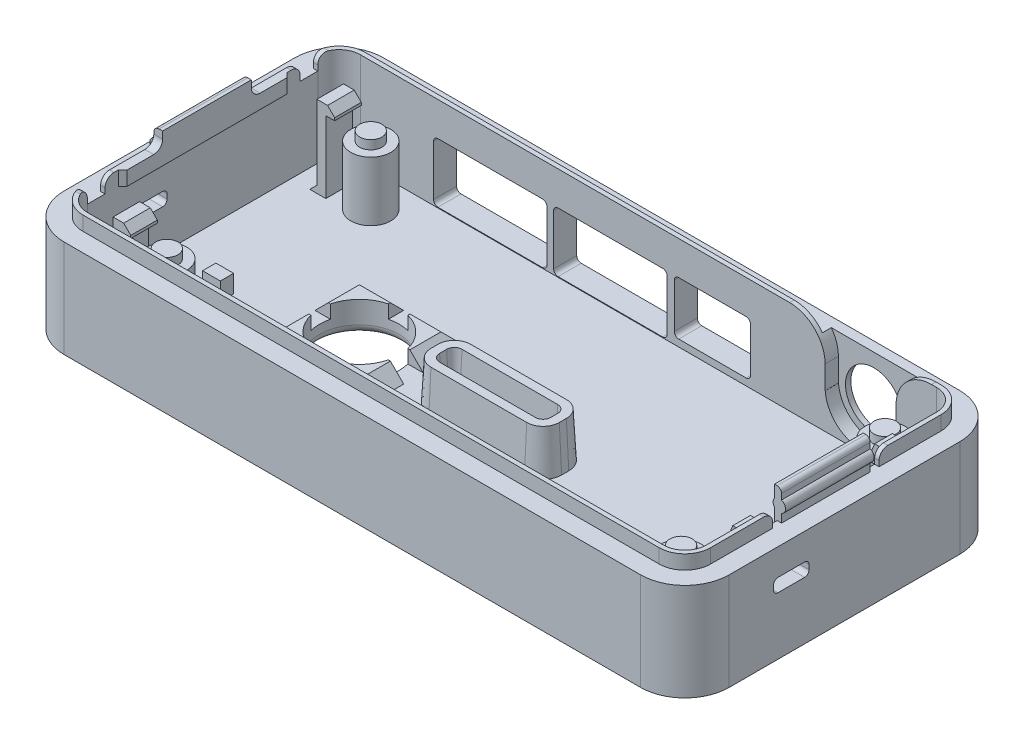
SolidWorks part; units mm, degrees
ref_plane "前视基准面" through (0, 0, 0) normal (0, 0, 1) x (1, 0, 0)
ref_plane "上视基准面" through (0, 0, 0) normal (0, 1, 0) x (1, 0, 0)
ref_plane "右视基准面" through (0, 0, 0) normal (1, 0, 0) x (0, 0, -1)
sketch "zero" plane through (0, 0, 0) normal (0, 1, 0) x (1, 0, 0)
  line L1 (-29.5, 15) -> (29.5, 15)
  line L2 (-32.5, 12) -> (-32.5, -12)
  line L3 (-29.5, -15) -> (29.5, -15)
  line L4 (32.5, 12) -> (32.5, -12)
  line L5 (-32.5, 15) -> (32.5, -15) construction
  line L6 (-32.5, -15) -> (32.5, 15) construction
  line L7 (-25.7, -15) -> (-14.5, -15)
  line L8 (-25.7, -15) -> (-25.7, -9.6569)
  line L9 (-25.7, -9.6569) -> (-14.5, -9.6569)
  line L10 (-14.5, -15) -> (-14.5, -9.6569)
  line L11 (5.2, -15) -> (12.7, -15)
  line L12 (5.2, -15) -> (5.2, -11)
  line L13 (5.2, -11) -> (12.7, -11)
  line L14 (12.7, -15) -> (12.7, -11)
  line L15 (17.8, -15) -> (25.3, -15)
  line L16 (17.8, -15) -> (17.8, -11)
  line L17 (17.8, -11) -> (25.3, -11)
  line L18 (25.3, -15) -> (25.3, -11)
  line L19 (-32.5, 7.7) -> (-19.5, 7.7)
  line L20 (-32.5, 7.7) -> (-32.5, -4.3)
  line L21 (-32.5, -4.3) -> (-19.5, -4.3)
  line L22 (-19.5, 7.7) -> (-19.5, -4.3)
  line L23 (-25.5, 14) -> (25.5, 14)
  line L24 (-25.5, 14) -> (-25.5, 8.8)
  line L25 (-25.5, 8.8) -> (25.5, 8.8)
  line L26 (25.5, 14) -> (25.5, 8.8)
  line L27 (-19.5, 7.2329) -> (-35.5, 7.2329)
  line L28 (-19.5, 7.2329) -> (-19.5, -3.7671)
  line L29 (-19.5, -3.7671) -> (-35.5, -3.7671)
  line L30 (-35.5, 7.2329) -> (-35.5, -3.7671)
  arc A0 (29.5, -15) -> (32.5, -12) centre (29.5, -12) ccw
  arc A1 (29.5, 15) -> (32.5, 12) centre (29.5, 12) cw
  arc A2 (-32.5, -12) -> (-29.5, -15) centre (-29.5, -12) ccw
  arc A3 (-29.5, 15) -> (-32.5, 12) centre (-29.5, 12) ccw
  circle A4 centre (-29, 11.4) radius 3
  circle A5 centre (-29, -11.5) radius 3
  circle A6 centre (29, 11.4) radius 3
  circle A7 centre (29, -11.5) radius 3
  circle A8 centre (-29, 11.4) radius 1.375
  circle A9 centre (-29, -11.5) radius 1.375
  circle A10 centre (29, -11.5) radius 1.375
  circle A11 centre (29, 11.4) radius 1.375
  point P0 (0, 0)
  dimension "D3" = 3
  dimension "D4" = 6
  dimension "D9" = 2.75
  dimension "D1" = 65
  dimension "D2" = 30
  dimension "D5" = 3.6
  dimension "D6" = 3.5
  dimension "D7" = 3.5
  dimension "D8" = 3.5
  dimension "D10" = 12
  dimension "D11" = 7.3
  dimension "D12" = 13
  dimension "D13" = 11.2
  dimension "D14" = 6.8
  dimension "D15" = 19.7
  dimension "D16" = 7.5
  dimension "D17" = 7.5
  dimension "D18" = 5.1
  dimension "D19" = 4
  dimension "D20" = 5.2
  dimension "D21" = 7
  dimension "D22" = 7
  dimension "D23" = 1
  dimension "D24" = 11
  dimension "D25" = 16
sketch "sugar" plane through (0, 0, 0) normal (0, 1, 0) x (1, 0, 0)
  line L1 (-29.5, 15) -> (29.5, 15)
  line L2 (-32.5, 12) -> (-32.5, -12)
  line L3 (-29.5, -15) -> (29.5, -15)
  line L4 (32.5, 12) -> (32.5, -12)
  line L5 (-32.5, 15) -> (32.5, -15) construction
  line L6 (-32.5, -15) -> (32.5, 15) construction
  line L7 (23.5, -11.5) -> (19.5, -11.5)
  line L8 (23.5, -11.5) -> (23.5, -13.9082)
  line L9 (23.5, -13.9082) -> (19.5, -13.9082)
  line L10 (19.5, -11.5) -> (19.5, -13.9082)
  line L11 (16, -11.0071) -> (8.5, -11.0071)
  line L12 (16, -11.0071) -> (16, -15)
  line L13 (16, -15) -> (8.5, -15)
  line L14 (8.5, -11.0071) -> (8.5, -15)
  line L15 (20.5, -13.9082) -> (22.5, -13.9082)
  line L16 (20.5, -13.9082) -> (20.5, -14.8173)
  line L17 (20.5, -14.8173) -> (22.5, -14.8173)
  line L18 (22.5, -13.9082) -> (22.5, -14.8173)
  arc A0 (29.5, 15) -> (32.5, 12) centre (29.5, 12) cw
  arc A1 (29.5, -15) -> (32.5, -12) centre (29.5, -12) ccw
  arc A2 (-32.5, -12) -> (-29.5, -15) centre (-29.5, -12) ccw
  arc A3 (-29.5, 15) -> (-32.5, 12) centre (-29.5, 12) ccw
  circle A4 centre (-29, 11.4) radius 3
  circle A5 centre (-29, 11.4) radius 1.375
  circle A6 centre (-29, -11.5) radius 3
  circle A7 centre (-29, -11.5) radius 1.375
  circle A8 centre (29, 11.4) radius 3
  circle A9 centre (29, 11.4) radius 1.375
  circle A10 centre (29, -11.5) radius 3
  circle A11 centre (29, -11.5) radius 1.375
  dimension "D3" = 3
  dimension "D1" = 65
  dimension "D2" = 30
  dimension "D4" = 9
  dimension "D5" = 4
  dimension "D6" = 3.5
  dimension "D7" = 7.5
  dimension "D8" = 2
  dimension "D9" = 1
sketch "case" plane through (0, 0, 0) normal (0, 1, 0) x (1, 0, 0)
  line L1 (-34.0422, 18) -> (30.9578, 18)
  line L2 (-39.0422, 13) -> (-39.0422, -13)
  line L3 (-34.0422, -18) -> (30.9578, -18)
  line L4 (35.9578, 13) -> (35.9578, -13)
  line L5 (-39.0422, 18) -> (35.9578, -18) construction
  line L6 (-39.0422, -18) -> (35.9578, 18) construction
  arc A0 (-39.0422, -13) -> (-34.0422, -18) centre (-34.0422, -13) ccw
  arc A1 (30.9578, -18) -> (35.9578, -13) centre (30.9578, -13) ccw
  arc A2 (30.9578, 18) -> (35.9578, 13) centre (30.9578, 13) cw
  arc A3 (-34.0422, 18) -> (-39.0422, 13) centre (-34.0422, 13) ccw
  point P0 (-1.5422, 0)
  point P3 (-1.5422, 0)
  dimension "D3" = 5
  dimension "D1" = 75
  dimension "D2" = 36
extrude "凸台-拉伸2" add sketch "case" along normal blind 11
sketch "草图2" plane through (0, 0, 0) normal (0, 1, 0) x (1, 0, 0)
  line L4 (-34.0422, -15.4) -> (30.9578, -15.4)
  line L5 (33.3578, -13) -> (33.3578, 13)
  line L6 (30.9578, 15.4) -> (-34.0422, 15.4)
  line L7 (-36.4422, 13) -> (-36.4422, -13)
  line L8 (33.8578, -13) -> (33.8578, 13)
  line L9 (30.9578, 15.9) -> (-34.0422, 15.9)
  line L10 (-36.9422, 13) -> (-36.9422, -13)
  line L11 (-34.0422, -15.9) -> (30.9578, -15.9)
  line L12 (33.8578, -13) -> (33.8578, 13)
  line L13 (30.9578, 15.9) -> (-34.0422, 15.9)
  line L14 (-36.9422, 13) -> (-36.9422, -13)
  line L15 (-34.0422, -15.9) -> (30.9578, -15.9)
  arc A4 (30.9578, -15.4) -> (33.3578, -13) centre (30.9578, -13) ccw
  arc A5 (33.3578, 13) -> (30.9578, 15.4) centre (30.9578, 13) ccw
  arc A6 (-34.0422, 15.4) -> (-36.4422, 13) centre (-34.0422, 13) ccw
  arc A7 (-36.4422, -13) -> (-34.0422, -15.4) centre (-34.0422, -13) ccw
  arc A8 (30.9578, -15.9) -> (33.8578, -13) centre (30.9578, -13) ccw
  arc A9 (33.8578, 13) -> (30.9578, 15.9) centre (30.9578, 13) ccw
  arc A10 (-34.0422, 15.9) -> (-36.9422, 13) centre (-34.0422, 13) ccw
  arc A11 (-36.9422, -13) -> (-34.0422, -15.9) centre (-34.0422, -13) ccw
  arc A12 (30.9578, -15.9) -> (33.8578, -13) centre (30.9578, -13) ccw
  arc A13 (33.8578, 13) -> (30.9578, 15.9) centre (30.9578, 13) ccw
  arc A14 (-34.0422, 15.9) -> (-36.9422, 13) centre (-34.0422, 13) ccw
  arc A15 (-36.9422, -13) -> (-34.0422, -15.9) centre (-34.0422, -13) ccw
  dimension "D1" = 2.1
  dimension "D2" = 0.5
ref_plane "基准面1" through (0, 11, 0) normal (0, 1, 0) x (1, 0, 0)
sketch "草图3" plane through (0, 11, 0) normal (0, 1, 0) x (1, 0, 0)
  line L4 (-34.0422, -15.4) -> (30.9578, -15.4)
  line L5 (33.3578, -13) -> (33.3578, 13)
  line L6 (30.9578, 15.4) -> (-34.0422, 15.4)
  line L7 (-36.4422, 13) -> (-36.4422, -13)
  line L8 (-34.0422, -15.4) -> (30.9578, -15.4)
  line L9 (33.3578, -13) -> (33.3578, 13)
  line L10 (30.9578, 15.4) -> (-34.0422, 15.4)
  line L11 (-36.4422, 13) -> (-36.4422, -13)
  line L12 (-36.9422, 13) -> (-36.9422, -13)
  line L13 (-34.0422, -15.9) -> (30.9578, -15.9)
  line L14 (33.8578, -13) -> (33.8578, 13)
  line L15 (30.9578, 15.9) -> (-34.0422, 15.9)
  line L16 (-36.9422, 13) -> (-36.9422, -13)
  line L17 (-34.0422, -15.9) -> (30.9578, -15.9)
  line L18 (33.8578, -13) -> (33.8578, 13)
  line L19 (30.9578, 15.9) -> (-34.0422, 15.9)
  arc A4 (30.9578, -15.4) -> (33.3578, -13) centre (30.9578, -13) ccw
  arc A5 (33.3578, 13) -> (30.9578, 15.4) centre (30.9578, 13) ccw
  arc A6 (-34.0422, 15.4) -> (-36.4422, 13) centre (-34.0422, 13) ccw
  arc A7 (-36.4422, -13) -> (-34.0422, -15.4) centre (-34.0422, -13) ccw
  arc A8 (30.9578, -15.4) -> (33.3578, -13) centre (30.9578, -13) ccw
  arc A9 (33.3578, 13) -> (30.9578, 15.4) centre (30.9578, 13) ccw
  arc A10 (-34.0422, 15.4) -> (-36.4422, 13) centre (-34.0422, 13) ccw
  arc A11 (-36.4422, -13) -> (-34.0422, -15.4) centre (-34.0422, -13) ccw
  arc A12 (-36.9422, -13) -> (-34.0422, -15.9) centre (-34.0422, -13) ccw
  arc A13 (30.9578, -15.9) -> (33.8578, -13) centre (30.9578, -13) ccw
  arc A14 (33.8578, 13) -> (30.9578, 15.9) centre (30.9578, 13) ccw
  arc A15 (-34.0422, 15.9) -> (-36.9422, 13) centre (-34.0422, 13) ccw
  arc A16 (-36.9422, -13) -> (-34.0422, -15.9) centre (-34.0422, -13) ccw
  arc A17 (30.9578, -15.9) -> (33.8578, -13) centre (30.9578, -13) ccw
  arc A18 (33.8578, 13) -> (30.9578, 15.9) centre (30.9578, 13) ccw
  arc A19 (-34.0422, 15.9) -> (-36.9422, 13) centre (-34.0422, 13) ccw
  dimension "D1" = 0
  dimension "D2" = 0
extrude "凸台-拉伸4" add sketch "草图3" along normal blind 1.6
sketch "草图5" plane through (0, 11, 0) normal (0, 1, 0) x (1, 0, 0)
  line L0 (33.3578, -13) -> (33.3578, 13) construction
  line L1 (33.0578, 5) -> (33.3578, 5)
  line L2 (33.0578, 5) -> (33.0578, -5)
  line L3 (33.0578, -5) -> (33.3578, -5)
  line L4 (33.3578, 5) -> (33.3578, -5)
  line L5 (33.0578, 5) -> (33.3578, -5) construction
  line L6 (33.0578, -5) -> (33.3578, 5) construction
  point P0 (33.2078, 0)
  dimension "D2" = 10
  dimension "D3" = 0.3
  dimension "D4" = 0
ref_plane "基准面3" through (33.8578, 0, 0) normal (1, 0, 0) x (0, 0, -1)
ref_plane "基准面7" through (-36.9422, 0, 0) normal (-1, 0, 0) x (0, 0, 1)
ref_plane "基准面8" through (0, 0, 0) normal (0, -1, 0) x (-1, 0, 0)
sketch "草图14" plane through (0, 11, 0) normal (0, 1, 0) x (1, 0, 0)
  line L4 (-34.0422, -15.4) -> (30.9578, -15.4)
  line L5 (33.3578, -13) -> (33.3578, 13)
  line L6 (30.9578, 15.4) -> (-34.0422, 15.4)
  line L7 (-36.4422, 13) -> (-36.4422, -13)
  line L8 (-34.0422, -15.4) -> (30.9578, -15.4)
  line L9 (33.3578, -13) -> (33.3578, 13)
  line L10 (30.9578, 15.4) -> (-34.0422, 15.4)
  line L11 (-36.4422, 13) -> (-36.4422, -13)
  arc A4 (30.9578, -15.4) -> (33.3578, -13) centre (30.9578, -13) ccw
  arc A5 (33.3578, 13) -> (30.9578, 15.4) centre (30.9578, 13) ccw
  arc A6 (-34.0422, 15.4) -> (-36.4422, 13) centre (-34.0422, 13) ccw
  arc A7 (-36.4422, -13) -> (-34.0422, -15.4) centre (-34.0422, -13) ccw
  arc A8 (30.9578, -15.4) -> (33.3578, -13) centre (30.9578, -13) ccw
  arc A9 (33.3578, 13) -> (30.9578, 15.4) centre (30.9578, 13) ccw
  arc A10 (-34.0422, 15.4) -> (-36.4422, 13) centre (-34.0422, 13) ccw
  arc A11 (-36.4422, -13) -> (-34.0422, -15.4) centre (-34.0422, -13) ccw
  dimension "D1" = 0
extrude "切除-拉伸2" cut sketch "草图14" against normal blind 9
extrude "凸台-拉伸12" add sketch "草图5" against normal blind 2 and the other way blind 1.6
sketch "草图15" plane through (0, 2, 0) normal (0, 1, 0) x (1, 0, 0)
  line L1 (35.9578, -13) -> (35.9578, 13) construction
  line L5 (-39.0422, 13) -> (-39.0422, -13) construction
  line L6 (-34.0422, -18) -> (30.9578, -18) construction
  line L7 (30.9578, 18) -> (-34.0422, 18) construction
  circle A0 centre (29.0603, -11.5295) radius 2.25
  circle A1 centre (-28.9397, -11.5295) radius 2.25
  circle A2 centre (29.0603, 11.4705) radius 2.25
  circle A3 centre (-28.9397, 11.4705) radius 2.25
  dimension "D1" = 4.5
  dimension "D2" = 6.8975
  dimension "D3" = 10.1025
  dimension "D4" = 6.4705
  dimension "D5" = 6.5295
extrude "凸台-拉伸13" add sketch "草图15" along normal blind 6.7
sketch "草图16" plane through (0, 8.7, 0) normal (0, 1, 0) x (1, 0, 0)
  circle A0 centre (29.0603, -11.5295) radius 1.25
  circle A1 centre (29.0603, 11.4705) radius 1.25
  circle A2 centre (-28.9397, -11.5295) radius 1.25
  circle A3 centre (-28.9397, 11.4705) radius 1.25
  point P12 (0, 0)
  dimension "D1" = 2.5
extrude "凸台-拉伸14" add sketch "草图16" along normal blind 1
sketch "草图17" plane through (0, 12.6, 0) normal (0, 1, 0) x (1, 0, 0)
  line L0 (33.3578, -13) -> (33.3578, -5) construction
  line L1 (33.3578, -5) -> (33.8578, -5)
  line L2 (33.3578, -5) -> (33.3578, -6)
  line L3 (33.3578, -6) -> (33.8578, -6)
  line L4 (33.8578, -5) -> (33.8578, -6)
  line L5 (33.3578, -13) -> (33.3578, 13) construction
  line L6 (33.8578, -13) -> (33.8578, 13) construction
  line L8 (33.3578, 5) -> (33.8578, 5)
  line L9 (33.3578, 5) -> (33.3578, 6)
  line L10 (33.3578, 6) -> (33.8578, 6)
  line L11 (33.8578, 5) -> (33.8578, 6)
  dimension "D1" = 1
  dimension "D2" = 1
extrude "切除-拉伸3" cut sketch "草图17" against normal blind 1.6
sketch "草图19" plane through (0, 12.6, 0) normal (0, 1, 0) x (1, 0, 0)
  line L0 (33.0578, 5) -> (33.0578, -5) construction
  line L1 (33.8578, -5) -> (33.0578, -5)
  line L2 (33.8578, -5) -> (33.8578, 5)
  line L3 (33.8578, 5) -> (33.0578, 5)
  line L4 (33.0578, -5) -> (33.0578, 5)
extrude "凸台-拉伸15" add sketch "草图19" along normal blind 1.8
sketch "草图20" plane through (0, 0, -5) normal (0, 0, -1) x (-1, 0, 0)
  line L0 (-30.9578, 11) -> (-35.9578, 11) construction
  line L3 (-33.8578, 11) -> (-33.8578, 14.4) construction
  circle A0 centre (-33.6078, 12.6) radius 0.7
  dimension "D1" = 1.4
  dimension "D2" = 1.6
  dimension "D3" = 0.25
extrude "凸台-拉伸16" add sketch "草图20" against normal blind 10
fillet "圆角4" radius 0.5 1 edges at (33.8578, 14.4, 0)
sketch "草图39" plane through (0, 0, -18) normal (0, 0, -1) x (-1, 0, 0)
  line L0 (-30.9578, 0) -> (34.0422, 0) construction
  line L1 (-35.9578, 11) -> (-35.9578, 0) construction
  circle A0 centre (-22.3721, 6.2789) radius 4
  dimension "D1" = 6.2789
  dimension "D3" = 8
  dimension "D2" = 13.5857
extrude "切除-拉伸4" cut sketch "草图39" against normal blind 0.5
sketch "草图41" plane through (0, 0, -18) normal (0, 0, -1) x (-1, 0, 0)
  line L0 (-30.9578, 0) -> (34.0422, 0) construction
  line L1 (-9.9578, 2.7789) -> (-1.3578, 2.7789)
  line L2 (-9.9578, 2.7789) -> (-9.9578, 8.7789)
  line L3 (-9.9578, 8.7789) -> (-1.3578, 8.7789)
  line L4 (-1.3578, 2.7789) -> (-1.3578, 8.7789)
  line L5 (-0.5578, 2.0789) -> (12.2422, 2.0789)
  line L6 (-0.5578, 2.0789) -> (-0.5578, 8.7789)
  line L7 (-0.5578, 8.7789) -> (12.2422, 8.7789)
  line L8 (12.2422, 2.0789) -> (12.2422, 8.7789)
  line L9 (12.9922, 2.0789) -> (25.7922, 2.0789)
  line L10 (12.9922, 2.0789) -> (12.9922, 8.7789)
  line L11 (12.9922, 8.7789) -> (25.7922, 8.7789)
  line L12 (25.7922, 2.0789) -> (25.7922, 8.7789)
  line L13 (-35.9578, 11) -> (-35.9578, 0) construction
  dimension "D1" = 8.7789
  dimension "D2" = 26
  dimension "D3" = 8.6
  dimension "D4" = 6
  dimension "D5" = 0.8
  dimension "D6" = 6.7
  dimension "D7" = 12.8
  dimension "D8" = 0.75
  dimension "D9" = 12.8
extrude "切除-拉伸5" cut sketch "草图41" against normal blind 12
sketch "草图42" plane through (0, 0, -17.5) normal (0, 0, -1) x (-1, 0, 0)
  circle A0 centre (-22.3721, 6.2789) radius 3.2
  circle A1 centre (-22.3721, 6.2789) radius 4 construction
extrude "切除-拉伸6" cut sketch "草图42" against normal blind 1.6
sketch "草图46" plane through (-36.4422, 0, 0) normal (1, 0, 0) x (0, 0, -1)
  line L0 (13, 12.6) -> (-13, 12.6) construction
  line L1 (-10, 12.6) -> (10, 12.6)
  line L2 (-10, 12.6) -> (-10, 11)
  line L3 (-10, 11) -> (10, 11)
  line L4 (10, 12.6) -> (10, 11)
  line L6 (-18, 11) -> (-18, 0) construction
  dimension "D1" = 8
  dimension "D2" = 8
extrude "凸台-拉伸19" add sketch "草图46" along normal blind 0.5
chamfer "倒角3" distance 1 angle 45 2 edges at (-35.9422, 11.8, -10) (-35.9422, 11.8, 10)
sketch "草图48" plane through (0, 12.6, 0) normal (0, 1, 0) x (1, 0, 0)
  line L0 (-35.9422, 9) -> (-35.9422, -9) construction
  line L1 (-35.9422, -5) -> (-36.9422, -5)
  line L2 (-35.9422, -5) -> (-35.9422, 5)
  line L3 (-35.9422, 5) -> (-36.9422, 5)
  line L4 (-36.9422, -5) -> (-36.9422, 5)
  line L5 (-36.9422, 13) -> (-36.9422, -13) construction
extrude "凸台-拉伸21" add sketch "草图48" along normal blind 1.8
sketch "草图49" plane through (0, 0, 5) normal (0, 0, 1) x (1, 0, 0)
  line L0 (-34.0422, 11) -> (-39.0422, 11) construction
  line L1 (-36.9422, 14.4) -> (-36.9422, 12.6) construction
  circle A0 centre (-36.6922, 12.6) radius 0.7
  dimension "D1" = 1.4
  dimension "D2" = 1.6
  dimension "D3" = 0.25
extrude "凸台-拉伸22" add sketch "草图49" against normal blind 10
sketch "草图50" plane through (0, 12.6, 0) normal (0, 1, 0) x (1, 0, 0)
  line L0 (-36.4422, 13) -> (-36.4422, 9.5) construction
  line L1 (-36.4422, 13) -> (-36.9422, 13)
  line L2 (-36.4422, 13) -> (-36.4422, 11)
  line L3 (-36.4422, 11) -> (-36.9422, 11)
  line L4 (-36.9422, 13) -> (-36.9422, 11)
  line L5 (-36.9422, 13) -> (-36.9422, 5) construction
  line L6 (-36.4422, -9.5) -> (-36.4422, -13) construction
  line L7 (-36.4422, -11) -> (-36.9422, -11)
  line L8 (-36.4422, -11) -> (-36.4422, -13)
  line L9 (-36.4422, -13) -> (-36.9422, -13)
  line L10 (-36.9422, -11) -> (-36.9422, -13)
  line L11 (-36.9422, -5) -> (-36.9422, -13) construction
  line L12 (30.9578, 18) -> (-34.0422, 18) construction
  line L13 (-34.0422, -18) -> (30.9578, -18) construction
  dimension "D1" = 2
  dimension "D2" = 2
  dimension "D3" = 5
  dimension "D4" = 5
extrude "切除-拉伸10" cut sketch "草图50" against normal blind 1.6
fillet "圆角9" radius 1 6 edges at (33.6078, 12.6, 6) (33.6078, 12.6, -6) (-36.6922, 12.6, -13) (-36.6922, 12.6, -11) (-36.6922, 12.6, 11) (-36.6922, 12.6, 13)
fillet "圆角10" radius 0.6 1 edges at (-36.9422, 14.4, 0)
sketch "草图51" plane through (0, 0, 0) normal (0, -1, 0) x (1, 0, 0)
  line L0 (35.9578, 13) -> (35.9578, -13) construction
  line L1 (6.2578, 2.3) -> (-5.7422, 2.3)
  line L2 (6.2578, 2.3) -> (6.2578, 4.3)
  line L3 (6.2578, 4.3) -> (-5.7422, 4.3)
  line L4 (-5.7422, 2.3) -> (-5.7422, 4.3)
  line L5 (30.9578, -18) -> (-34.0422, -18) construction
  dimension "D1" = 2
  dimension "D2" = 12
  dimension "D3" = 29.7
  dimension "D4" = 20.3
extrude "切除-拉伸11" cut sketch "草图51" against normal blind 2
fillet "圆角13" radius 0.6 4 edges at (-5.7422, 1, 4.3) (-5.7422, 1, 2.3) (6.2578, 1, 4.3) (6.2578, 1, 2.3)
sketch "草图52" plane through (0, 2, 0) normal (0, 1, 0) x (1, 0, 0)
  line L0 (-11.5279, -7.2295) -> (-20.7279, -7.2295)
  line L5 (-20.7279, -7.2295) -> (-20.7279, 1.9705)
  line L6 (-11.5279, 1.9705) -> (-20.7279, 1.9705)
  line L7 (-11.5279, -7.2295) -> (-11.5279, 1.9705)
  line L8 (-39.0422, 13) -> (-39.0422, -13) construction
  line L9 (-34.0422, -18) -> (30.9578, -18) construction
  dimension "D1" = 9.2
  dimension "D2" = 9.2
  dimension "D3" = 18.3143
  dimension "D4" = 10.7705
extrude "凸台-拉伸23" add sketch "草图52" along normal blind 1.5
chamfer "倒角5" distance 1.5 angle 45 4 edges at (-16.1279, 2, -1.9705) (-11.5279, 2, 2.6295) (-16.1279, 2, 7.2295) (-20.7279, 2, 2.6295)
sketch "草图53" plane through (0, 0, 0) normal (0, -1, 0) x (1, 0, 0)
  line L1 (30.9578, -18) -> (-34.0422, -18) construction
  line L2 (-39.0422, -13) -> (-39.0422, 13) construction
  circle A0 centre (-16.1279, 2.6295) radius 4.5
  dimension "D1" = 9
  dimension "D2" = 20.6295
  dimension "D3" = 22.9143
extrude "切除-拉伸12" cut sketch "草图53" against normal up to next
fillet "圆角14" radius 1 1 edges at (-16.1279, 0, -1.8705)
sketch "草图55" plane through (0, 3.5, 0) normal (0, 1, 0) x (1, 0, 0)
  line L1 (-10.0279, -3.7295) -> (-22.2279, -3.7295)
  line L2 (-10.0279, -3.7295) -> (-10.0279, -1.5295)
  line L3 (-10.0279, -1.5295) -> (-22.2279, -1.5295)
  line L4 (-22.2279, -3.7295) -> (-22.2279, -1.5295)
  line L5 (-10.0279, -3.7295) -> (-22.2279, -1.5295) construction
  line L6 (-10.0279, -1.5295) -> (-22.2279, -3.7295) construction
  circle A0 centre (-16.1279, -2.6295) radius 4.5 construction
  point P0 (-16.1279, -2.6295)
  dimension "D1" = 12.2
  dimension "D2" = 2.2
extrude "切除-拉伸13" cut sketch "草图55" against normal blind 1.5
sketch "草图56" plane through (0, 3.5, 0) normal (0, 1, 0) x (1, 0, 0)
  line L1 (-15.0279, -8.7295) -> (-17.2279, -8.7295)
  line L2 (-15.0279, -8.7295) -> (-15.0279, 3.4705)
  line L3 (-15.0279, 3.4705) -> (-17.2279, 3.4705)
  line L4 (-17.2279, -8.7295) -> (-17.2279, 3.4705)
  line L5 (-15.0279, -8.7295) -> (-17.2279, 3.4705) construction
  line L6 (-15.0279, 3.4705) -> (-17.2279, -8.7295) construction
  arc A0 (-11.7644, -3.7295) -> (-11.7644, -1.5295) centre (-16.1279, -2.6295) ccw construction
  point P0 (-16.1279, -2.6295)
  dimension "D1" = 12.2
  dimension "D2" = 2.2
extrude "切除-拉伸14" cut sketch "草图56" against normal blind 1.5
sketch "草图62" plane through (0, 0, 0) normal (0, -1, 0) x (1, 0, 0)
  line L54 (31.3299, 13.3324) -> (30.9169, 13.5642)
  line L55 (30.9169, 13.5642) -> (28.7745, 14.7678)
  line L56 (28.7745, 14.7678) -> (28.3615, 15.0024)
  line L57 (27.5011, 14.9926) -> (27.0935, 14.7486)
  line L58 (27.0935, 14.7486) -> (24.9793, 13.4962)
  line L60 (24.9793, 13.4962) -> (24.5717, 13.255)
  line L61 (24.15, 12.5065) -> (24.189, 9.0989)
  line L62 (24.6278, 8.3602) -> (25.0408, 8.1284)
  line L63 (25.0408, 8.1284) -> (27.1831, 6.9248)
  line L65 (27.1831, 6.9248) -> (27.5962, 6.6902)
  line L66 (28.4566, 6.7) -> (28.8641, 6.9441)
  line L67 (28.8641, 6.9441) -> (30.9784, 8.1964)
  line L68 (30.9784, 8.1964) -> (31.3859, 8.4376)
  line L69 (31.8076, 9.1861) -> (31.7686, 12.5937)
  line L70 (25.1226, 12.9222) -> (27.7378, 14.4738)
  line L73 (28.1396, 14.4784) -> (30.7754, 12.9841)
  line L74 (30.7822, 12.6337) -> (28.2554, 11.0831)
  line L75 (29.0741, 8.5137) -> (28.7797, 8.3451)
  line L76 (28.7517, 8.2963) -> (28.7615, 7.4416)
  line L77 (28.7336, 7.3928) -> (28.1845, 7.0731)
  line L78 (28.1013, 7.1205) -> (28.0711, 9.7589)
  line L79 (28.099, 9.8076) -> (29.0331, 10.3512)
  line L80 (31.0237, 8.7127) -> (30.4803, 8.3959)
  line L81 (30.3971, 8.4434) -> (30.3827, 9.6998)
  line L82 (30.4107, 9.7486) -> (30.9541, 10.0626)
  line L83 (31.0373, 10.0151) -> (31.0517, 8.7615)
  line L84 (29.0341, 9.0205) -> (28.7735, 8.8864)
  line L85 (28.7443, 8.9459) -> (28.7366, 9.6183)
  line L86 (28.7646, 9.6671) -> (29.008, 9.8066)
  line L129 (28.7735, 8.8864) -> (28.7797, 8.3451)
  line L130 (28.7443, 8.9459) -> (28.7517, 8.2963)
  spline S0 degree 3 poles (28.3615, 15.0024) (28.2268, 15.075) (28.0782, 15.1132) (27.93, 15.1115) knots 3 3 3 3 4 4 4 4
  spline S1 degree 3 poles (27.93, 15.1115) (27.7818, 15.1098) (27.6341, 15.0682) (27.5011, 14.9926) knots 4 4 4 4 5 5 5 5
  spline S2 degree 3 poles (24.5717, 13.255) (24.3085, 13.0981) (24.1465, 12.8113) (24.15, 12.5065) knots 8 8 8 8 9 9 9 9
  spline S3 degree 3 poles (24.189, 9.0989) (24.1926, 8.7912) (24.3611, 8.511) (24.6278, 8.3602) knots 10 10 10 10 11 11 11 11
  spline S4 degree 3 poles (27.5962, 6.6902) (27.7309, 6.6148) (27.8795, 6.5794) (28.0277, 6.5811) knots 14 14 14 14 15 15 15 15
  spline S5 degree 3 poles (28.0277, 6.5811) (28.1759, 6.5828) (28.3236, 6.6216) (28.4566, 6.7) knots 15 15 15 15 16 16 16 16
  spline S6 degree 3 poles (31.3859, 8.4376) (31.652, 8.5945) (31.8112, 8.8784) (31.8076, 9.1861) knots 19 19 19 19 20 20 20 20
  spline S7 degree 3 poles (31.7686, 12.5937) (31.7651, 12.8986) (31.5995, 13.1816) (31.3299, 13.3324) knots 21 21 21 21 22 22 22 22
  spline S8 degree 2 poles (27.6998, 11.0768) (25.1072, 12.5345) (25.1014, 12.5373) knots 0 0 0 1 1 1
  spline S9 degree 3 poles (25.1014, 12.5373) (24.9664, 12.6326) (24.9783, 12.838) (25.1226, 12.9222) knots 1 1 1 1 2 2 2 2
  spline S10 degree 3 poles (27.7378, 14.4738) (27.8595, 14.5465) (28.0134, 14.5482) (28.1396, 14.4784) knots 3 3 3 3 4 4 4 4
  spline S11 degree 3 poles (30.7754, 12.9841) (30.9101, 12.9087) (30.9152, 12.715) (30.7822, 12.6337) knots 5 5 5 5 6 6 6 6
  spline S12 degree 3 poles (28.2554, 11.0831) (28.0856, 10.9815) (27.8719, 10.979) (27.6998, 11.0768) knots 7 7 7 7 8 8 8 8
  spline S13 degree 3 poles (28.7615, 7.4416) (28.7618, 7.4216) (28.7534, 7.4044) (28.7336, 7.3928) knots 3 3 3 3 4 4 4 4
  spline S14 degree 3 poles (28.1845, 7.0731) (28.1477, 7.0527) (28.1018, 7.0778) (28.1013, 7.1205) knots 5 5 5 5 6 6 6 6
  spline S15 degree 3 poles (28.0711, 9.7589) (28.0708, 9.7788) (28.0792, 9.7988) (28.099, 9.8076) knots 7 7 7 7 8 8 8 8
  spline S16 degree 3 poles (29.0331, 10.3512) (29.6389, 10.7029) (30.1424, 10.7771) (30.1502, 10.0933) knots 9 9 9 9 10 10 10 10
  spline S17 degree 3 poles (30.1502, 10.0933) (30.1577, 9.4351) (29.6544, 8.8509) (29.0741, 8.5137) knots 10 10 10 10 11 11 11 11
  spline S18 degree 3 poles (31.0517, 8.7615) (31.0519, 8.7415) (31.0407, 8.7214) (31.0237, 8.7127) knots 0 0 0 0 1 1 1 1
  spline S19 degree 3 poles (30.4803, 8.3959) (30.4435, 8.3755) (30.3976, 8.4006) (30.3971, 8.4434) knots 2 2 2 2 3 3 3 3
  spline S20 degree 3 poles (30.3827, 9.6998) (30.3825, 9.7198) (30.3937, 9.737) (30.4107, 9.7486) knots 4 4 4 4 5 5 5 5
  spline S21 degree 3 poles (30.9541, 10.0626) (30.991, 10.0829) (31.0368, 10.0578) (31.0373, 10.0151) knots 6 6 6 6 7 7 7 7
  spline S22 degree 3 poles (30.6996, 10.8946) (30.9175, 11.0224) (31.0748, 10.9701) (31.0771, 10.7707) (31.0794, 10.5741) (30.9253, 10.3415) (30.7073, 10.2165) knots 2 2 2 2 3 3 3 4 4 4 4
  spline S23 degree 3 poles (30.7073, 10.2165) (30.4866, 10.0857) (30.3293, 10.1381) (30.327, 10.3346) (30.3247, 10.5369) (30.4788, 10.7667) (30.6996, 10.8946) knots 0 0 0 0 1 1 1 2 2 2 2
  spline S24 degree 3 poles (29.5048, 9.7183) (29.5079, 9.4476) (29.3569, 9.2065) (29.0341, 9.0205) knots 0 0 0 0 1 1 1 1
  spline S25 degree 3 poles (28.7366, 9.6183) (28.7364, 9.6382) (28.7475, 9.6583) (28.7646, 9.6671) knots 4 4 4 4 5 5 5 5
  spline S26 degree 3 poles (29.008, 9.8066) (29.325, 9.9926) (29.5016, 9.9975) (29.5048, 9.7183) knots 6 6 6 6 7 7 7 7
fillet "圆角17" radius 1 2 edges at (-36.4422, 12.6, 5) (-36.4422, 12.6, -5)
sketch "草图63" plane through (0, 2, 0) normal (0, 1, 0) x (1, 0, 0)
  line L0 (30.9578, 15.4) -> (-34.0422, 15.4) construction
  line L1 (-30.4422, -4.5) -> (-28.4422, -4.5)
  line L2 (-30.4422, -4.5) -> (-30.4422, -6)
  line L3 (-30.4422, -6) -> (-28.4422, -6)
  line L4 (-28.4422, -4.5) -> (-28.4422, -6)
  line L5 (-36.4422, 13) -> (-36.4422, -13) construction
  dimension "D1" = 2
  dimension "D2" = 1.5
  dimension "D3" = 19.9
  dimension "D4" = 6
extrude "凸台-拉伸24" add sketch "草图63" along normal blind 2
fillet "圆角18" radius 0.5 12 edges at (1.3578, 8.7789, -16.7) (9.9578, 8.7789, -16.7) (9.9578, 2.7789, -16.7) (1.3578, 2.7789, -16.7) (-12.2422, 2.0789, -16.7) (0.5578, 2.0789, -16.7) (0.5578, 8.7789, -16.7) (-12.2422, 8.7789, -16.7) (-25.7922, 8.7789, -16.7) (-12.9922, 8.7789, -16.7) (-25.7922, 2.0789, -16.7) (-12.9922, 2.0789, -16.7)
sketch "草图66" plane through (0, 2, 0) normal (0, 1, 0) x (1, 0, 0)
  line L8 (-5.1422, -0.8) -> (5.6578, -0.8)
  line L9 (-7.2422, -3.7) -> (-7.2422, -2.9)
  line L10 (5.6578, -5.8) -> (-5.1422, -5.8)
  line L11 (7.7578, -2.9) -> (7.7578, -3.7)
  arc A8 (7.7578, -2.9) -> (5.6578, -0.8) centre (5.6578, -2.9) ccw
  arc A9 (-5.1422, -0.8) -> (-7.2422, -2.9) centre (-5.1422, -2.9) ccw
  arc A10 (-7.2422, -3.7) -> (-5.1422, -5.8) centre (-5.1422, -3.7) ccw
  arc A11 (5.6578, -5.8) -> (7.7578, -3.7) centre (5.6578, -3.7) ccw
extrude "凸台-拉伸27" add sketch "草图66" along normal blind 5 draft 3
extrude "切除-拉伸15" cut sketch "草图62" against normal blind 0.5
sketch "草图67" plane through (-39.0422, 0, 0) normal (-1, 0, 0) x (0, 0, 1)
  line L0 (18, 11) -> (18, 0) construction
  line L1 (4, 8) -> (8, 8)
  line L2 (4, 8) -> (4, 6.5)
  line L3 (4, 6.5) -> (8, 6.5)
  line L4 (8, 8) -> (8, 6.5)
  line L5 (-13, 11) -> (13, 11) construction
  dimension "D1" = 4
  dimension "D2" = 1.5
  dimension "D3" = 10
  dimension "D4" = 3
extrude "切除-拉伸16" cut sketch "草图67" against normal up to next
fillet "圆角20" radius 0.5 4 edges at (-37.7422, 6.5, 8) (-37.7422, 8, 8) (-37.7422, 8, 4) (-37.7422, 6.5, 4)
sketch "草图68" plane through (33.3578, 0, 0) normal (-1, 0, 0) x (0, 0, 1)
  line L0 (8, 7) -> (8, 7.5) construction
  line L1 (4.5, 6.5) -> (7.5, 6.5) construction
  line L2 (4, 7.5) -> (4, 7) construction
  line L3 (7.5, 8) -> (4.5, 8) construction
  line L4 (8, 7) -> (8, 7.5)
  line L5 (4.5, 6.5) -> (7.5, 6.5)
  line L6 (4, 7.5) -> (4, 7)
  line L7 (7.5, 8) -> (4.5, 8)
  arc A0 (8, 7.5) -> (7.5, 8) centre (7.5, 7.5) ccw construction
  arc A1 (7.5, 6.5) -> (8, 7) centre (7.5, 7) ccw construction
  arc A2 (4, 7) -> (4.5, 6.5) centre (4.5, 7) ccw construction
  arc A3 (4.5, 8) -> (4, 7.5) centre (4.5, 7.5) ccw construction
  arc A4 (8, 7.5) -> (7.5, 8) centre (7.5, 7.5) ccw
  arc A5 (7.5, 6.5) -> (8, 7) centre (7.5, 7) ccw
  arc A6 (4, 7) -> (4.5, 6.5) centre (4.5, 7) ccw
  arc A7 (4.5, 8) -> (4, 7.5) centre (4.5, 7.5) ccw
extrude "切除-拉伸17" cut sketch "草图68" against normal up to next
sketch "草图70" plane through (0, 2, 0) normal (0, -1, 0) x (1, 0, 0)
  line L0 (5.6578, 4.3) -> (-5.1422, 4.3) construction
  line L1 (-5.7422, 3.7) -> (-5.7422, 2.9) construction
  line L2 (-5.1422, 2.3) -> (5.6578, 2.3) construction
  line L3 (6.2578, 2.9) -> (6.2578, 3.7) construction
  line L4 (6.2578, 2.9) -> (6.2578, 3.7)
  line L5 (-5.1422, 2.3) -> (5.6578, 2.3)
  line L6 (-5.7422, 3.7) -> (-5.7422, 2.9)
  line L7 (5.6578, 4.3) -> (-5.1422, 4.3)
  arc A0 (6.2578, 3.7) -> (5.6578, 4.3) centre (5.6578, 3.7) ccw construction
  arc A1 (-5.1422, 4.3) -> (-5.7422, 3.7) centre (-5.1422, 3.7) ccw construction
  arc A2 (-5.7422, 2.9) -> (-5.1422, 2.3) centre (-5.1422, 2.9) ccw construction
  arc A3 (5.6578, 2.3) -> (6.2578, 2.9) centre (5.6578, 2.9) ccw construction
  arc A4 (6.2578, 3.7) -> (5.6578, 4.3) centre (5.6578, 3.7) ccw
  arc A5 (5.6578, 2.3) -> (6.2578, 2.9) centre (5.6578, 2.9) ccw
  arc A6 (-5.7422, 2.9) -> (-5.1422, 2.3) centre (-5.1422, 2.9) ccw
  arc A7 (-5.1422, 4.3) -> (-5.7422, 3.7) centre (-5.1422, 3.7) ccw
extrude "切除-拉伸18" cut sketch "草图70" against normal up to next (5 mm away) draft 3 draft outward yes
sketch "草图71" plane through (33.3578, 0, 0) normal (-1, 0, 0) x (0, 0, 1)
  line L0 (13, 2) -> (-13, 2) construction
  line L1 (-9, 12) -> (-7, 12)
  line L2 (-9, 12) -> (-9, 10)
  line L3 (-9, 10) -> (-7, 10)
  line L4 (-7, 12) -> (-7, 10)
  line L5 (7, 12) -> (9, 12)
  line L6 (7, 12) -> (7, 10)
  line L7 (7, 10) -> (9, 10)
  line L8 (9, 12) -> (9, 10)
  line L10 (-18, 11) -> (-18, 0) construction
  line L11 (18, 11) -> (18, 0) construction
  dimension "D1" = 2
  dimension "D2" = 2
  dimension "D3" = 2
  dimension "D4" = 8
  dimension "D5" = 9
  dimension "D6" = 9
extrude "凸台-拉伸28" add sketch "草图71" along normal blind 1.8
chamfer "倒角6" distance 0.8 angle 68 2 edges at (31.5578, 12, 8) (31.5578, 12, -8) first distance on face at (32.4578, 12, 8) first distance on face at (32.4578, 12, -8)
sketch "草图73" plane through (0, 2, 0) normal (0, 1, 0) x (1, 0, 0)
  line L0 (30.9578, 18) -> (-34.0422, 18) construction
  line L1 (-33.5422, 13) -> (-32.5422, 13)
  line L2 (-33.5422, 13) -> (-33.5422, 10)
  line L3 (-33.5422, 10) -> (-32.5422, 10)
  line L4 (-32.5422, 13) -> (-32.5422, 10)
  line L5 (-33.5422, -10) -> (-32.5422, -10)
  line L6 (-33.5422, -10) -> (-33.5422, -13)
  line L7 (-33.5422, -13) -> (-32.5422, -13)
  line L8 (-32.5422, -10) -> (-32.5422, -13)
  line L9 (-34.0422, -18) -> (30.9578, -18) construction
  line L10 (-39.0422, 13) -> (-39.0422, -13) construction
  dimension "D1" = 5
  dimension "D2" = 3
  dimension "D3" = 3
  dimension "D4" = 5
  dimension "D5" = 1
  dimension "D6" = 1
  dimension "D7" = 5.5
  dimension "D8" = 5.5
extrude "凸台-拉伸30" add sketch "草图73" along normal blind 9.2
sketch "草图74" plane through (-32.5422, 0, 0) normal (1, 0, 0) x (0, 0, -1)
  line L0 (10, 11.2) -> (10, 2) construction
  line L1 (10, 11.2) -> (13, 11.2)
  line L2 (10, 11.2) -> (10, 10.1)
  line L3 (10, 10.1) -> (13, 10.1)
  line L4 (13, 11.2) -> (13, 10.1)
  line L5 (10, 11.2) -> (13, 11.2) construction
  line L6 (13, 11.2) -> (13, 2) construction
  line L7 (-13, 11.2) -> (-10, 11.2) construction
  line L8 (-13, 11.2) -> (-10, 11.2)
  line L9 (-13, 11.2) -> (-13, 10.1)
  line L10 (-13, 10.1) -> (-10, 10.1)
  line L11 (-10, 11.2) -> (-10, 10.1)
  line L12 (-10, 11.2) -> (-10, 2) construction
  dimension "D1" = 1.1
  dimension "D2" = 1.1
extrude "凸台-拉伸31" add sketch "草图74" along normal blind 1
chamfer "倒角7" distance 0.8 angle 45 4 edges at (-33.5422, 2, 11.5) (-33.5422, 2, -11.5) (-31.5422, 11.2, 11.5) (-31.5422, 11.2, -11.5)
sketch "草图75" plane through (0, 0, -15.4) normal (0, 0, 1) x (1, 0, 0)
  circle A0 centre (22.3721, 6.2789) radius 4
extrude "切除-拉伸19" cut sketch "草图75" against normal blind 1.5
sketch "草图76" plane through (0, 0, -15.4) normal (0, 0, 1) x (1, 0, 0)
  line L0 (30.9578, 12.6) -> (-34.0422, 12.6) construction
  line L1 (18.3721, 12.6) -> (26.3721, 12.6)
  line L2 (18.3721, 12.6) -> (18.3721, 5.9883)
  line L3 (18.3721, 5.9883) -> (26.3721, 5.9883)
  line L4 (26.3721, 12.6) -> (26.3721, 5.9883)
  line L5 (18.3721, 12.6) -> (26.3721, 5.9883) construction
  line L6 (18.3721, 5.9883) -> (26.3721, 12.6) construction
  circle A1 centre (22.3721, 6.2789) radius 4 construction
  point P0 (22.3721, 9.2942)
  point P5 (0, 0)
  point P8 (0, 0)
  point P11 (0, 0)
  dimension "D2" = 8
  dimension "D1" = 0
extrude "切除-拉伸20" cut sketch "草图76" against normal blind 1.5
fillet "圆角21" radius 4 2 edges at (26.3721, 12.6, -15.65) (18.3721, 12.6, -15.65)
